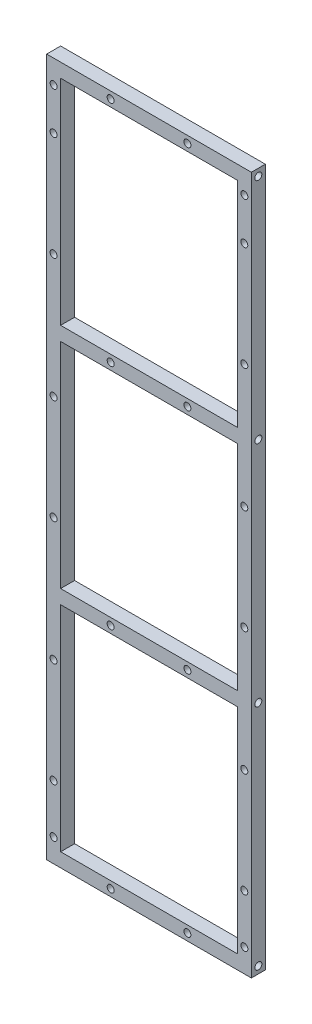
SolidWorks part; units mm, degrees
ref_plane "Front Plane" through (0, 0, 0) normal (0, 0, 1) x (1, 0, 0)
ref_plane "Top Plane" through (0, 0, 0) normal (0, 1, 0) x (1, 0, 0)
ref_plane "Right Plane" through (0, 0, 0) normal (1, 0, 0) x (0, 0, -1)
sketch "Sketch1" plane through (0, 0, 0) normal (0, 0, 1) x (1, 0, 0)
  line L0 (38, 144) -> (38, 52)
  line L9 (-44, -150) -> (44, -150)
  line L10 (-44, -150) -> (-44, 150)
  line L11 (-44, 150) -> (44, 150)
  line L12 (44, -150) -> (44, 150)
  line L15 (-38, -144) -> (38, -144)
  line L16 (-38, -144) -> (-38, -52)
  line L17 (-38, 144) -> (38, 144)
  line L21 (-38, 52) -> (38, 52)
  line L23 (-38, 46) -> (38, 46)
  line L25 (-38, -46) -> (38, -46)
  line L27 (-38, -52) -> (38, -52)
  line L33 (38, 46) -> (38, -46)
  line L34 (-38, 52) -> (-38, 144)
  line L35 (-38, -46) -> (-38, 46)
  line L36 (38, -52) -> (38, -144)
  point P0 (0, 0)
  point P4 (0, -46)
  point P6 (0, 0)
  point P20 (0, 0)
  point P21 (0, -150)
  dimension "D1" = 88
  dimension "D2" = 300
  dimension "D3" = 76
  dimension "D4" = 288
  dimension "D5" = 6
  dimension "D6" = 92
  dimension "D7" = 6
  dimension "D8" = 92
  dimension "D9" = 6
  dimension "D10" = 6
  dimension "D11" = 92
extrude "Boss-Extrude1" add sketch "Sketch1" along normal blind 6
sketch "Sketch2" plane through (44, 0, 0) normal (1, 0, 0) x (0, 0, -1)
  line L0 (-6, 150) -> (0, 150) construction
  circle A0 centre (-3, 147) radius 1.5
  circle A1 centre (-3, 49) radius 1.5
  circle A2 centre (-3, -49) radius 1.5
  circle A3 centre (-3, -147) radius 1.5
  dimension "D1" = 3
  dimension "D2" = 4
extrude "Cut-Extrude1" cut sketch "Sketch2" against normal blind 10
mirror "Mirror1" about plane through (0, 0, 0) normal (1, 0, 0) of "Cut-Extrude1"
sketch "Sketch3" plane through (0, 0, 6) normal (0, 0, 1) x (1, 0, 0)
  line L0 (-44, 150) -> (44, 150) construction
  line L1 (-44, -150) -> (-44, 150) construction
  circle A0 centre (-41, 140) radius 1.5
  circle A1 centre (41, 140) radius 1.5
  circle A2 centre (41, -140) radius 1.5
  circle A3 centre (-41, -140) radius 1.5
  dimension "D1" = 10
  dimension "D2" = 3
  dimension "D3" = 2
  dimension "D4" = 2
extrude "Cut-Extrude2" cut sketch "Sketch3" against normal blind 10
sketch "Sketch4" plane through (0, 0, 6) normal (0, 0, 1) x (1, 0, 0)
  line L0 (-44, -150) -> (-44, 150) construction
  line L1 (44, -150) -> (44, 150) construction
  line L2 (-44, 150) -> (44, 150) construction
  circle A0 centre (-16.5, 147) radius 1.5
  circle A1 centre (16.5, 147) radius 1.5
  circle A2 centre (16.5, 49) radius 1.5
  circle A3 centre (-16.5, 49) radius 1.5
  circle A4 centre (16.5, -49) radius 1.5
  circle A5 centre (-16.5, -49) radius 1.5
  circle A6 centre (16.5, -147) radius 1.5
  circle A7 centre (-16.5, -147) radius 1.5
  circle A8 centre (-41.0409, 122) radius 1.5
  circle A9 centre (-41.0409, 77) radius 1.5
  circle A10 centre (40.9591, 122) radius 1.5
  circle A11 centre (40.9591, 77) radius 1.5
  circle A12 centre (40.9591, 24) radius 1.5
  circle A13 centre (40.9591, -21) radius 1.5
  circle A14 centre (40.9591, -74) radius 1.5
  circle A15 centre (40.9591, -119) radius 1.5
  circle A16 centre (-41.0409, 24) radius 1.5
  circle A17 centre (-41.0409, -21) radius 1.5
  circle A18 centre (-41.0409, -74) radius 1.5
  circle A19 centre (-41.0409, -119) radius 1.5
  dimension "D1" = 27.5
  dimension "D4" = 45
  dimension "D7" = 2
  dimension "D2" = 27.5
  dimension "D3" = 4
  dimension "D5" = 28
  dimension "D6" = 28
  dimension "D8" = 3
extrude "Cut-Extrude3" cut sketch "Sketch4" against normal blind 10
